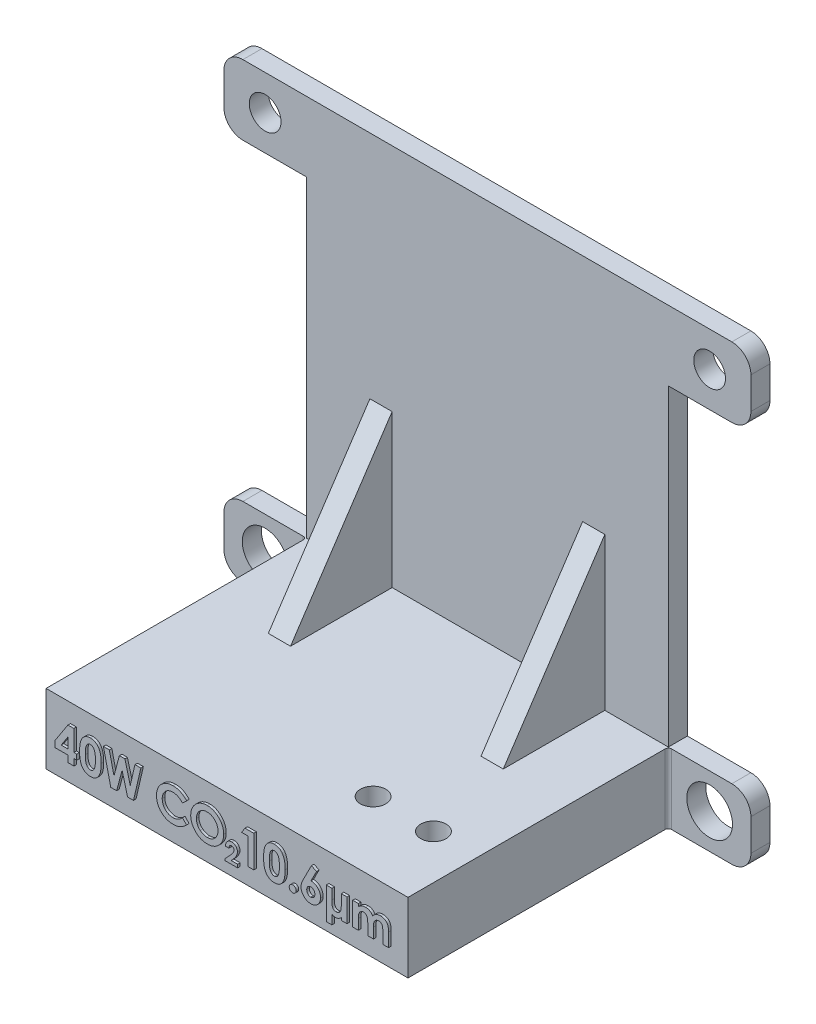
SolidWorks part; units mm, degrees
ref_plane "Front Plane" through (0, 0, 0) normal (0, 0, 1) x (1, 0, 0)
ref_plane "Top Plane" through (0, 0, 0) normal (0, 1, 0) x (1, 0, 0)
ref_plane "Right Plane" through (0, 0, 0) normal (1, 0, 0) x (0, 0, -1)
sketch "Sketch1" plane through (0, 0, 0) normal (0, 0, 1) x (1, 0, 0)
  line L0 (28.5, -35.63) -> (41.5, -35.63)
  line L1 (-35, -30.13) -> (35, -30.13) construction
  line L2 (-35, -30.13) -> (-35, 30.13) construction
  line L3 (-35, 30.13) -> (35, 30.13) construction
  line L4 (35, -30.13) -> (35, 30.13) construction
  line L5 (-35, -30.13) -> (35, 30.13) construction
  line L6 (-35, 30.13) -> (35, -30.13) construction
  line L7 (-41.5, -35.63) -> (-28.5, -35.63)
  line L8 (-41.5, -35.63) -> (-41.5, -24.63)
  line L9 (-41.5, -24.63) -> (-28.5, -24.63)
  line L11 (-41.5, -35.63) -> (-28.5, -24.63) construction
  line L12 (-41.5, -24.63) -> (-28.5, -35.63) construction
  line L14 (28.5, -24.63) -> (41.5, -24.63)
  line L15 (41.5, -35.63) -> (41.5, -24.63)
  line L16 (28.5, -35.63) -> (41.5, -24.63) construction
  line L17 (28.5, -24.63) -> (41.5, -35.63) construction
  line L18 (28.5, 24.63) -> (41.5, 24.63)
  line L20 (28.5, 35.63) -> (41.5, 35.63)
  line L21 (41.5, 24.63) -> (41.5, 35.63)
  line L22 (28.5, 24.63) -> (41.5, 35.63) construction
  line L23 (28.5, 35.63) -> (41.5, 24.63) construction
  line L24 (-41.5, 24.63) -> (-28.5, 24.63)
  line L25 (-41.5, 24.63) -> (-41.5, 35.63)
  line L26 (-41.5, 35.63) -> (-28.5, 35.63)
  line L28 (-41.5, 24.63) -> (-28.5, 35.63) construction
  line L29 (-41.5, 35.63) -> (-28.5, 24.63) construction
  line L30 (-28.5, -24.63) -> (-28.5, 24.63)
  line L31 (-28.5, -35.63) -> (-7, -35.63)
  line L32 (28.5, -24.63) -> (28.5, 24.63)
  line L33 (-28.5, 35.63) -> (28.5, 35.63)
  line L34 (7, -39.63) -> (7, -35.63)
  line L35 (28.5, 24.63) -> (28.5, 35.63) [skipped]
  line L36 (-7, -39.63) -> (-7, -35.63)
  line L37 (28.5, -35.63) -> (28.5, -24.63) [skipped]
  line L38 (7, -35.63) -> (28.5, -35.63)
  circle A0 centre (-35, 30.13) radius 2.5
  circle A1 centre (35, 30.13) radius 2.5
  circle A2 centre (-35, -30.13) radius 3.6
  circle A3 centre (35, -30.13) radius 3.6
  circle A4 centre (0, -39.63) radius 3.5
  arc A5 (-7, -39.63) -> (7, -39.63) centre (0, -39.63) ccw
  point P0 (0, 0)
  dimension "D3" = 5
  dimension "D4" = 5
  dimension "D5" = 7.2
  dimension "D6" = 7.2
  dimension "D13" = 7
  dimension "D15" = 14
  dimension "D1" = 60.26
  dimension "D2" = 70
  dimension "D7" = 11
  dimension "D8" = 13
  dimension "D11" = 57
  dimension "D12" = 49.26
  dimension "D14" = 4
  dimension "D9" = 2
  dimension "D10" = 2
extrude "Boss-Extrude1" add sketch "Sketch1" along normal blind 3
sketch "Sketch3" plane through (0, 0, 3) normal (0, 0, 1) x (1, 0, 0)
  line L0 (-41.5, -35.63) -> (-7, -35.63) construction
  line L1 (-28.5, -24.63) -> (28.5, -24.63)
  line L2 (-28.5, -24.63) -> (-28.5, -35.63)
  line L3 (-28.5, -35.63) -> (28.5, -35.63)
  line L4 (28.5, -24.63) -> (28.5, -35.63)
  line L5 (28.5, -24.63) -> (28.5, 24.63) construction
extrude "Boss-Extrude2" add sketch "Sketch3" along normal blind 41
ref_plane "Plane1" through (0, 0, 0) normal (1, 0, 0) x (0, 0, -1)
sketch "Sketch5" plane through (0, 0, 0) normal (1, 0, 0) x (0, 0, -1)
  line L0 (-19, -24.63) -> (-3, -0.63)
  line L1 (-44, -24.63) -> (-3, -24.63) construction
  line L2 (-3, -24.63) -> (-3, 24.63) construction
  dimension "D1" = 16
  dimension "D2" = 24
rib "Rib2" sketch "Sketch5" sketch "Sketch5" thickness 37 extrusion direction parallel to sketch draft on no parameters "D1"=37
sketch "Sketch6" plane through (0, 0, 0) normal (1, 0, 0) x (0, 0, -1)
  line L0 (-19, -24.63) -> (-3, -0.63)
  line L1 (-3, -0.63) -> (-3, -24.63)
  line L2 (-3, -24.63) -> (-19, -24.63)
extrude "Cut-Extrude1" cut sketch "Sketch6" against normal mid plane 30
fillet "Fillet2" radius 3 10 edges at (41.5, 24.63, 1.5) (-41.5, 35.63, 1.5) (-41.5, -35.63, 1.5) (-41.5, 24.63, 1.5) (-41.5, -24.63, 1.5) (41.5, -35.63, 1.5) (41.5, -24.63, 1.5) (41.5, 35.63, 1.5) (-7, -35.63, 1.5) (7, -35.63, 1.5)
sketch "Sketch7" plane through (0, -24.63, 0) normal (0, 1, 0) x (1, 0, 0)
  line L0 (28.5, -44) -> (28.5, -3) construction
  line L1 (28.5, -44) -> (-28.5, -44) construction
  circle A0 centre (21.5, -33) radius 2
  circle A2 centre (12, -33) radius 2
  dimension "D3" = 4
  dimension "D4" = 4
  dimension "D1" = 7
  dimension "D2" = 11
  dimension "D5" = 9.5
extrude "Cut-Extrude2" cut sketch "Sketch7" against normal through all
fillet "Fillet6" radius 0.5 3 edges at (-28.5, -30.13, 3) (28.5, -30.13, 3) (0, -35.63, 3)
sketch "Sketch8" plane through (0, 0, 44) normal (0, 0, 1) x (1, 0, 0)
  line L0 (-28.5, -32.63) -> (28.5, -32.63) construction
  line L1 (-28.5, -24.63) -> (-28.5, -35.63) construction
  line L2 (28.5, -35.63) -> (28.5, -24.63) construction
  line L3 (-28.5, -33.63) -> (28.5, -33.63) construction
  line L4 (-28.5, -24.63) -> (-28.5, -35.63) construction
  line L6 (-28.5, -35.63) -> (28.5, -35.63) construction
  text T0 "<b>40W CO 10.6μm</b>" font "Century Gothic" height 5
  text T1 "<b>  2</b>" font "Century Gothic" height 3
  dimension "D1" = 3
  dimension "D2" = 2
extrude "Boss-Extrude3" add sketch "Sketch8" along normal blind 0.4
